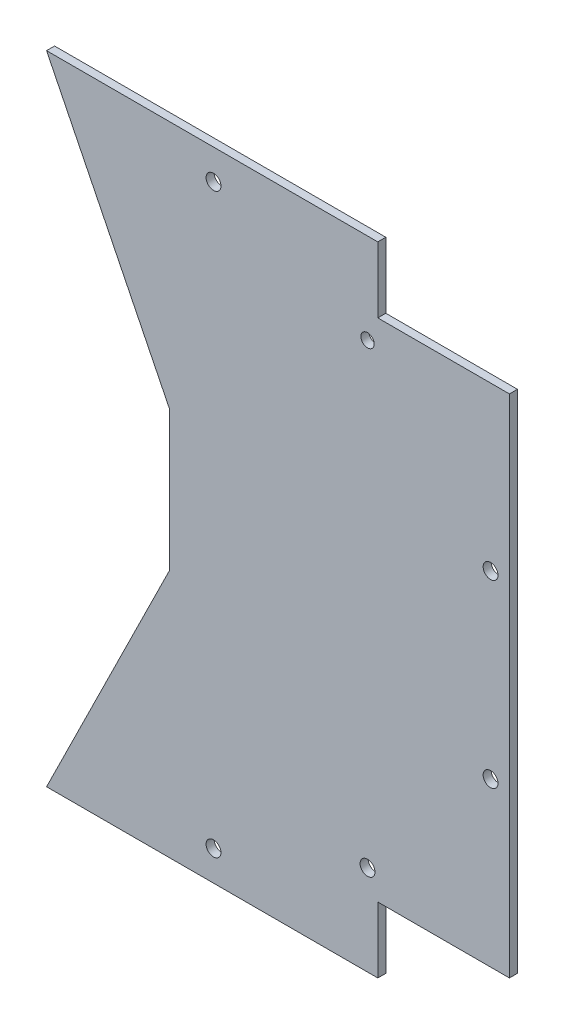
SolidWorks part; units mm, degrees
material "Thornel Mat VMA"
ref_plane "Front Plane" through (0, 0, 0) normal (0, 0, 1) x (1, 0, 0)
ref_plane "Top Plane" through (0, 0, 0) normal (0, 1, 0) x (1, 0, 0)
ref_plane "Right Plane" through (0, 0, 0) normal (1, 0, 0) x (0, 0, -1)
sketch "Sketch2" plane through (0, 0, 0) normal (0, 0, 1) x (-1, 0, 0)
  line L11 (-2.9301, 168.7083) -> (38.7094, 168.7083)
  line L12 (-2.9301, 8.6883) -> (38.7094, 8.6883)
  line L13 (38.7094, -12.1397) -> (38.7094, 8.6883)
  line L14 (143.4971, -12.1397) -> (38.7094, -12.1397)
  line L15 (38.7094, 189.5363) -> (38.7094, 168.7083)
  line L16 (143.4971, 189.5363) -> (38.7094, 189.5363)
  line L17 (104.6174, 110.8598) -> (143.4971, 189.5363)
  line L18 (104.6174, 66.5368) -> (143.4971, -12.1397)
  line L19 (104.6174, 66.5368) -> (72.8674, 66.5368)
  line L20 (72.8674, 66.5368) -> (72.8674, 110.8598)
  line L21 (104.6174, 110.8598) -> (72.8674, 110.8598)
  line L22 (-2.9301, 168.7083) -> (-2.9301, 8.6883)
  line L23 (41.9566, 19.6103) -> (41.9566, 13.2603) construction
  circle A0 centre (41.9566, 160.9613) radius 2.3495
  circle A1 centre (90.6739, 180.0113) radius 2.3495
  circle A2 centre (90.6739, -2.6147) radius 2.3495
  circle A3 centre (3.0351, 117.2098) radius 2.3495
  circle A4 centre (3.0351, 60.1868) radius 2.3495
  circle A5 centre (41.9566, 16.4353) radius 2.0955
  point P36 (41.9566, 16.4353)
  dimension "D3" = 4.699
  dimension "D7" = 31.75
  dimension "D8" = 41.6395
  dimension "D9" = 20.828
  dimension "D10" = 160.02
  dimension "D11" = 20.828
  dimension "D12" = 41.6395
  dimension "D13" = 104.7876
  dimension "D14" = 116.297
  dimension "D15" = 116.297
  dimension "D16" = 44.323
  dimension "D17" = 26.297
  dimension "D18" = 9.525
  dimension "D19" = 28.575
  dimension "D20" = 7.747
  dimension "D21" = 51.9645
  dimension "D22" = 51.4985
  dimension "D23" = 5.9651
  dimension "D24" = 51.4985
  dimension "D25" = 5.9651
  dimension "D26" = 7.747
  dimension "D27" = 3.2471
  dimension "D28" = 9.525
  dimension "D29" = 51.9645
extrude "Boss-Extrude1" add sketch "Sketch2" along normal blind 2.54
sketch "Sketch3" plane through (0, 0, 2.54) normal (0, 0, 1) x (1, 0, 0)
  line L1 (-104.6174, -66.5368) -> (-72.8674, -66.5368)
  line L2 (-104.6174, -66.5368) -> (-104.6174, -110.8598)
  line L3 (-104.6174, -110.8598) -> (-72.8674, -110.8598)
  line L4 (-72.8674, -66.5368) -> (-72.8674, -110.8598)
extrude "Boss-Extrude2" add sketch "Sketch3" against normal up to surface (2.54 mm away) up to face at (-65.9118, -88.6983, 0)
